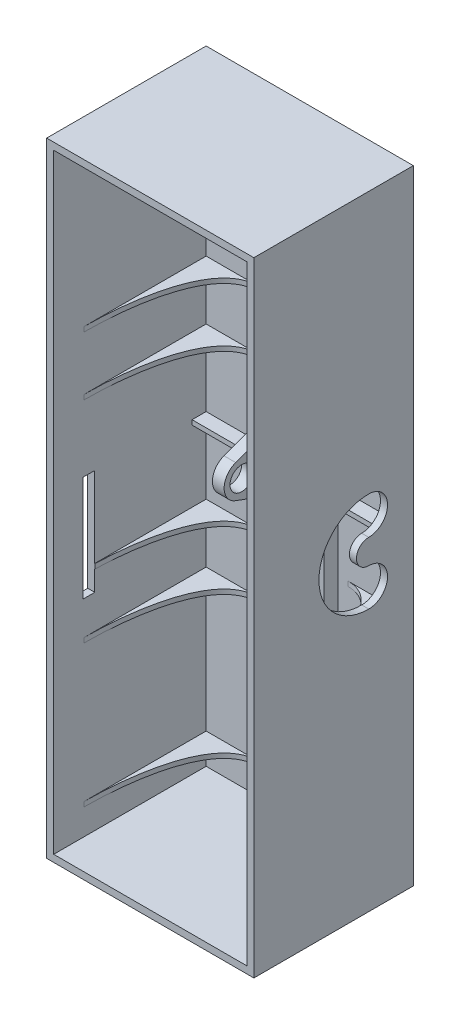
SolidWorks part; units mm, degrees
ref_plane "Front Plane" through (0, 0, 0) normal (0, 0, 1) x (1, 0, 0)
ref_plane "Top Plane" through (0, 0, 0) normal (0, 1, 0) x (1, 0, 0)
ref_plane "Right Plane" through (0, 0, 0) normal (1, 0, 0) x (0, 0, -1)
sketch "Sketch1" plane through (0, 0, 0) normal (0, 0, 1) x (1, 0, 0)
  line L0 (0, 263) -> (0, 0)
  line L1 (0, 0) -> (88.35, 0)
  line L3 (3, 3) -> (85.35, 3)
  line L7 (0, 263) -> (3, 263)
  line L8 (3, 3) -> (3, 263)
  line L11 (85.35, 3) -> (85.35, 263.0928)
  line L12 (85.35, 263.0928) -> (88.35, 263.0928)
  line L13 (88.35, 0) -> (88.35, 263.0928)
  dimension "D1" = 3
  dimension "D2" = 3
  dimension "D3" = 260
  dimension "D4" = 82.35
  dimension "D5" = 3
extrude "Boss-Extrude1" add sketch "Sketch1" along normal blind 68
sketch "Sketch2" plane through (0, 0, 0) normal (0, 0, 1) x (1, 0, 0)
  line L1 (0, 263) -> (88.35, 263)
  line L2 (0, 263) -> (0, 0)
  line L3 (0, 0) -> (88.35, 0)
  line L4 (88.35, 263) -> (88.35, 0)
extrude "Boss-Extrude2" add sketch "Sketch2" along normal blind 3
ref_plane "Plane1" through (34.175, 0, 0) normal (1, 0, 0) x (0, 0, -1)
sketch "Sketch3" plane through (34.175, 0, 0) normal (1, 0, 0) x (0, 0, -1)
  line L2 (-21.5652, 140.0477) -> (-3, 146.8049)
  line L3 (-3, 3) -> (-3, 263) construction
  line L4 (-3, 146.8049) -> (-3, 119.1951)
  line L5 (-3, 119.1951) -> (-21.5652, 125.9523)
  line L7 (-68, 3) -> (-3, 3) construction
  arc A0 (-21.5652, 140.0477) -> (-21.5652, 125.9523) centre (-19, 133) ccw
  circle A1 centre (-19, 133) radius 5
  dimension "D2" = 15
  dimension "D5" = 10
  dimension "D1" = 16
  dimension "D3" = 130
  dimension "D4" = 70
extrude "Boss-Extrude3" add sketch "Sketch3" against normal blind 5
ref_plane "Plane2" through (54.175, 0, 0) normal (1, 0, 0) x (0, 0, -1)
sketch "Sketch6" plane through (54.175, 0, 0) normal (1, 0, 0) x (0, 0, -1)
  line L0 (-19, 138) -> (-3, 138)
  line L2 (-3, 138) -> (-3, 128)
  line L3 (-3, 128) -> (-19, 128)
  line L4 (-3, 263) -> (-3, 3) construction
  arc A0 (-19, 138) -> (-19, 128) centre (-19, 133) ccw
  circle A1 centre (-19, 133) radius 5 construction
extrude "Boss-Extrude6" add sketch "Sketch6" along normal blind 8
hole_wizard "M6 Clearance Hole1" positions "Sketch7" profile "Sketch8" hole size "M6" standard "ISO" end condition up to next
sketch "Sketch7" plane through (54.175, 0, 0) normal (-1, 0, 0) x (0, 0, 1)
  arc A0 (19, 128) -> (19, 138) centre (19, 133) ccw construction
  point P0 (19, 133)
sketch "Sketch8" plane through (54.175, 133, 19) normal (0, 1, 0) x (0, 0, 1)
  line L0 (0, 0) -> (0, 8)
  line L1 (0, 8) -> (3.3, 8)
  line L2 (3.3, 8) -> (3.3, 0)
  line L5 (3.3, 0) -> (0, 0)
  line L11 (0, -6.35) -> (0, 107.95) construction
  dimension "Thru Hole Dia." = 6.6
  dimension "Thru Hole Depth" = 8
sketch "Sketch10" plane through (85.35, 0, 0) normal (-1, 0, 0) x (0, 0, 1)
  line L2 (3, 263) -> (3, 3) construction
  line L4 (19, 146.25) -> (19, 119.75) construction
  arc A0 (19, 146.25) -> (19, 119.75) centre (19, 133) cw construction
  arc A1 (19, 111.75) -> (19, 154.25) centre (19, 133) ccw
  arc A2 (19, 127.75) -> (19, 138.25) centre (19, 133) ccw
  arc A3 (19, 127.75) -> (19, 111.75) centre (19, 119.75) ccw
  arc A4 (19, 154.25) -> (19, 138.25) centre (19, 146.25) ccw
  point P5 (32.25, 133)
  point P20 (3, 133)
  dimension "D3" = 8
  dimension "D1" = 16
  dimension "D2" = 13.25
extrude "Cut-Extrude1" cut sketch "Sketch10" against normal up to next
sketch "Sketch11" plane through (0, 263, 0) normal (0, 1, 0) x (1, 0, 0)
  line L4 (0, 0) -> (0, -68)
  line L5 (88.35, 0) -> (0, 0)
  line L6 (88.35, -68) -> (88.35, 0)
  line L7 (0, -68) -> (88.35, -68)
  line L8 (0, 0) -> (0, -68)
  line L9 (88.35, 0) -> (0, 0)
  line L10 (88.35, -68) -> (88.35, 0)
  line L11 (0, -68) -> (88.35, -68)
  dimension "D1" = 0
extrude "Boss-Extrude7" add sketch "Sketch11" along normal blind 3
ref_plane "Plane4" through (44.175, 0, 0) normal (1, 0, 0) x (0, 0, -1)
sketch "Sketch13" plane through (0, 0, 3) normal (0, 0, 1) x (1, 0, 0)
  line L0 (3, 3) -> (3, 263) construction
  line L1 (3, 251.9797) -> (24.8525, 251.9797)
  line L2 (3, 251.9797) -> (3, 249.9797)
  line L3 (3, 249.9797) -> (24.8525, 249.9797)
  line L4 (24.8525, 251.9797) -> (24.8525, 249.9797)
  line L5 (3, 3) -> (3, 263) construction
  line L6 (3, 191.4189) -> (24.8525, 191.4189)
  line L7 (3, 191.4189) -> (3, 189.4189)
  line L8 (3, 189.4189) -> (24.8525, 189.4189)
  line L9 (24.8525, 191.4189) -> (24.8525, 189.4189)
  line L10 (3, 166.3498) -> (24.8525, 166.3498)
  line L11 (3, 166.3498) -> (3, 164.3498)
  line L12 (3, 164.3498) -> (24.8525, 164.3498)
  line L13 (24.8525, 166.3498) -> (24.8525, 164.3498)
  line L14 (3, 133) -> (85.35, 133) construction
  line L15 (85.35, 263) -> (85.35, 3) construction
  line L16 (3, 16.0203) -> (24.8525, 16.0203)
  line L17 (24.8525, 14.0203) -> (24.8525, 16.0203)
  line L18 (3, 14.0203) -> (24.8525, 14.0203)
  line L19 (3, 14.0203) -> (3, 16.0203)
  line L20 (3, 76.5811) -> (24.8525, 76.5811)
  line L21 (24.8525, 74.5811) -> (24.8525, 76.5811)
  line L22 (3, 74.5811) -> (24.8525, 74.5811)
  line L23 (3, 74.5811) -> (3, 76.5811)
  line L24 (3, 101.6502) -> (24.8525, 101.6502)
  line L25 (24.8525, 99.6502) -> (24.8525, 101.6502)
  line L26 (3, 99.6502) -> (24.8525, 99.6502)
  line L27 (3, 99.6502) -> (3, 101.6502)
  dimension "D1" = 2
extrude "Boss-Extrude8" add sketch "Sketch13" along normal blind 52
sketch "Sketch14" plane through (0, 14.0203, 0) normal (0, -1, 0) x (1, 0, 0)
  line L0 (3, 3) -> (24.8525, 3) construction
  line L1 (3, 55) -> (3, 3) construction
  line L2 (24.8525, 3) -> (24.8525, 55)
  line L3 (24.8525, 55) -> (3, 55)
  spline S0 degree 3 poles (3, 55) (3, 38.0721) (6.2716, 3) (24.8525, 3) knots 0 0 0 0 1 1 1 1
extrude "Cut-Extrude2" cut sketch "Sketch14" against normal up to surface (237.9595 mm away) up to face at (13.9263, 251.9797, 29)
mirror "Mirror3" about plane through (44.175, 0, 0) normal (1, 0, 0) of "Boss-Extrude8", "Cut-Extrude2"
sketch "Sketch15" plane through (0, 0, 3) normal (0, 0, 1) x (1, 0, 0)
  line L0 (85.35, 263) -> (3, 263) construction
  line L1 (30.675, 263) -> (32.675, 263)
  line L2 (30.675, 263) -> (30.675, 3)
  line L3 (30.675, 3) -> (32.675, 3)
  line L4 (32.675, 263) -> (32.675, 3)
  line L5 (85.35, 3) -> (3, 3) construction
  line L6 (29.175, 119.1951) -> (34.175, 119.1951) construction
  line L7 (3, 263) -> (85.35, 263) construction
  line L8 (59.175, 263) -> (57.175, 263)
  line L9 (59.175, 263) -> (59.175, 3)
  line L10 (59.175, 3) -> (57.175, 3)
  line L11 (57.175, 263) -> (57.175, 3)
  line L12 (62.175, 128) -> (54.175, 128) construction
  line L13 (29.175, 119.1951) -> (29.175, 146.8049) construction
  line L14 (29.175, 134) -> (3, 134)
  line L15 (29.175, 134) -> (29.175, 132)
  line L16 (29.175, 132) -> (3, 132)
  line L17 (3, 134) -> (3, 132)
  line L18 (3, 101.6502) -> (3, 164.3498) construction
  line L19 (62.175, 128) -> (62.175, 138) construction
  line L20 (62.175, 134) -> (85.35, 134)
  line L21 (62.175, 134) -> (62.175, 132)
  line L22 (62.175, 132) -> (85.35, 132)
  line L23 (85.35, 134) -> (85.35, 132)
  line L24 (85.35, 263) -> (85.35, 3) construction
  line L25 (29.175, 140.0477) -> (29.175, 125.9523) construction
  point P10 (31.675, 119.1951)
  point P11 (31.675, 3)
  point P18 (58.175, 3)
  point P21 (58.175, 128)
  point P38 (62.175, 133)
  point P39 (29.175, 133)
  dimension "D1" = 2
extrude "Boss-Extrude9" add sketch "Sketch15" along normal blind 6
sketch "Sketch16" plane through (0, 0, 3) normal (0, 0, 1) x (1, 0, 0)
  line L1 (36.675, 258) -> (51.675, 258)
  line L2 (36.675, 258) -> (36.675, 208)
  line L3 (36.675, 208) -> (51.675, 208)
  line L4 (51.675, 258) -> (51.675, 208)
  line L5 (54.175, 138) -> (54.175, 128) construction
  line L7 (34.175, 133) -> (54.175, 133) construction
  line L8 (34.175, 119.1951) -> (34.175, 146.8049) construction
  line L9 (36.675, 58) -> (51.675, 58)
  line L10 (51.675, 8) -> (51.675, 58)
  line L11 (36.675, 8) -> (51.675, 8)
  line L12 (36.675, 8) -> (36.675, 58)
  line L13 (88.35, 266) -> (0, 266) construction
  point P10 (54.175, 133)
  point P11 (51.675, 233)
  point P20 (44.175, 266)
  point P21 (44.175, 258)
  dimension "D1" = 15
  dimension "D2" = 50
  dimension "D3" = 100
extrude "Boss-Extrude10" add sketch "Sketch16" along normal blind 4
hole_wizard "M6 Tapped Hole2" positions "Sketch17" profile "Sketch18" tap size "M6" standard "ISO" end condition up to next
sketch "Sketch17" plane through (0, 0, 7) normal (0, 0, 1) x (1, 0, 0)
  line L0 (51.675, 258) -> (36.675, 258) construction
  line L1 (36.675, 208) -> (51.675, 208) construction
  line L2 (51.675, 58) -> (36.675, 58) construction
  line L3 (36.675, 8) -> (51.675, 8) construction
  point P0 (44.175, 250.24)
  point P2 (44.175, 215.76)
  point P4 (44.175, 50.24)
  point P6 (44.175, 15.76)
  point P18 (44.175, 8)
  dimension "D1" = 7.76
  dimension "D2" = 7.76
  dimension "D3" = 7.76
  dimension "D4" = 7.76
sketch "Sketch18" plane through (44.175, 250.24, 7) normal (1, 0, 0) x (0, -1, 0)
  line L0 (0, 0) -> (0, 7)
  line L1 (0, 7) -> (2.5, 7)
  line L2 (2.5, 7) -> (2.5, 0)
  line L5 (2.5, 0) -> (0, 0)
  line L11 (0, -6.35) -> (0, 107.95) construction
  dimension "Thru Tap Drill Dia." = 5
  dimension "Thru Tap Drill Depth" = 7
cosmetic thread "Hole Thread2" parameters "D2"=6
cosmetic thread "Hole Thread3" parameters "D2"=6
cosmetic thread "Hole Thread4" parameters "D2"=6
cosmetic thread "Hole Thread5" parameters "D2"=6
sketch "Sketch20" plane through (3, 0, 0) normal (1, 0, 0) x (0, 0, -1)
  line L0 (-68, 3) -> (-68, 263) construction
  line L1 (-55.5, 136) -> (-50.5, 136)
  line L2 (-55.5, 136) -> (-55.5, 91)
  line L3 (-55.5, 91) -> (-50.5, 91)
  line L4 (-50.5, 136) -> (-50.5, 91)
  line L6 (0, 266) -> (-68, 266) construction
  dimension "D1" = 45
  dimension "D2" = 12.5
  dimension "D3" = 5
  dimension "D4" = 175
extrude "Cut-Extrude4" cut sketch "Sketch20" against normal mid plane 20
